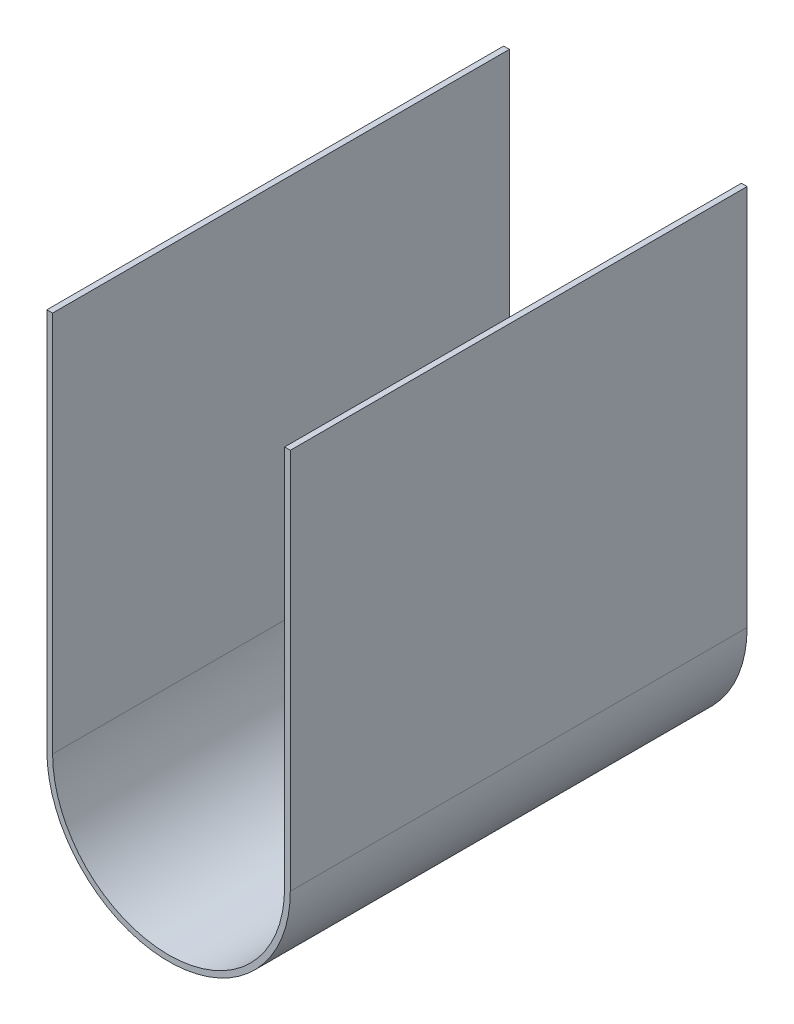
SolidWorks part; units mm, degrees
ref_plane "Front Plane" through (0, 0, 0) normal (0, 0, 1) x (1, 0, 0)
ref_plane "Top Plane" through (0, 0, 0) normal (0, 1, 0) x (1, 0, 0)
ref_plane "Right Plane" through (0, 0, 0) normal (1, 0, 0) x (0, 0, -1)
sketch "Sketch1" plane through (0, 0, 0) normal (0, 0, 1) x (1, 0, 0)
  line L1 (-32.5, -95) -> (32.5, -95)
  line L2 (-32.5, -95) -> (-32.5, 95)
  line L3 (-32.5, 95) -> (32.5, 95)
  line L4 (32.5, -95) -> (32.5, 95)
  line L5 (-32.5, -95) -> (32.5, 95) construction
  line L6 (-32.5, 95) -> (32.5, -95) construction
  line L7 (15.5, -110.5) -> (-15.5, -110.5)
  line L8 (15.5, -110.5) -> (15.5, -79.5)
  line L9 (15.5, -79.5) -> (-15.5, -79.5)
  line L10 (-15.5, -110.5) -> (-15.5, -79.5)
  line L11 (15.5, -110.5) -> (-15.5, -79.5) construction
  line L12 (15.5, -79.5) -> (-15.5, -110.5) construction
  circle A0 centre (0, -95) radius 32.5
  circle A1 centre (0, -95) radius 42 construction
  circle A2 centre (0, -95) radius 14
  point P0 (0, 0)
  point P14 (0, -127.5)
  dimension "D1" = 84
  dimension "D4" = 28
  dimension "D2" = 31
  dimension "D3" = 31
  dimension "D5" = 65
  dimension "D6" = 190
  dimension "D7" = 222.5
extrude "Boss-Extrude1" add sketch "Sketch1" along normal blind 6 contours A0 L4 L3 L2 | L1 A0 L10 L9 L8 | L1 A0 L8 L7 L10 | A2 L1 L10 L7 L8 | A2 L1 L8 L9 L10 region at (0, -78.7429, 0) region at (0, 12.6028, 0) region at (0, -111.2571, 0) region at (-15.1534, -87.25, 0) region at (-14.75, -95.3466, 0)
hole_wizard "M3 Clearance Hole1" positions "Sketch2" profile "Sketch3" hole size "M3" standard "ANSI Metric"
sketch "Sketch2" plane through (0, 0, 0) normal (0, 0, -1) x (-1, 0, 0)
  point P0 (-15.5, -110.5)
  point P3 (15.5, -110.5)
  point P6 (15.5, -79.5)
  point P9 (-15.5, -79.5)
sketch "Sketch3" plane through (15.5, -110.5, 0) normal (1, 0, 0) x (0, 1, 0)
  line L0 (0, 0) -> (0, 7.0815)
  line L1 (0, 7.0815) -> (1.8, 6)
  line L2 (1.8, 6) -> (1.8, 0)
  line L5 (1.8, 0) -> (0, 0)
  line L10 (0, 7.0815) -> (-1.8, 6) construction
  line L11 (0, -6.35) -> (0, 107.95) construction
  dimension "Hole Dia." = 3.6
  dimension "Hole Depth" = 6
  dimension "Drill Angle" = 118
fillet "Fillet1" radius 15 2 edges at (-32.5, 95, 3) (32.5, 95, 3)
sketch "Sketch4" plane through (0, 0, 6) normal (0, 0, 1) x (1, 0, 0)
  line L0 (32.5, -95) -> (32.5, 80) construction
  line L1 (32.5, -65) -> (-32.5, -65)
  line L2 (32.5, -65) -> (32.5, -56)
  line L3 (32.5, -56) -> (-32.5, -56)
  line L4 (-32.5, -65) -> (-32.5, -56)
  line L5 (-32.5, -95) -> (-32.5, 80) construction
  line L6 (0, 12) -> (0, 3)
  line L7 (32.5, 80) -> (-32.5, 80)
  line L8 (32.5, 80) -> (32.5, 71)
  line L9 (32.5, 71) -> (-32.5, 71)
  line L10 (-32.5, 80) -> (-32.5, 71)
  line L11 (-32.5, 12) -> (32.5, 12)
  line L12 (-32.5, 12) -> (-32.5, 3)
  line L13 (-32.5, 3) -> (32.5, 3)
  line L14 (32.5, 12) -> (32.5, 3)
  point P20 (0, 7.5)
  line M15 (-32.5, 80) -> (-32.5, -95)
  line M17 (32.5, -95) -> (32.5, 80)
  dimension "D1" = 9
  dimension "D2" = 9
  dimension "D3" = 9
  dimension "D4" = 30
  dimension "D5" = 127
  dimension "D6" = 63.5
extrude "Cut-Extrude1" cut sketch "Sketch4" against normal blind 2 contours L9 L7 M17 M15 | L13 L6 L11 M15 | L6 L13 L11 M17 | L3 L1 M17 M15 region at (0, -60.5, 6) region at (16.25, 7.5, 6) region at (-16.25, 7.5, 6) region at (0, 75.5, 6)
hole_wizard "M4 Clearance Hole1" positions "Sketch5" profile "Sketch6" hole size "M4" standard "ANSI Metric"
sketch "Sketch5" plane through (0, 0, 4) normal (0, 0, 1) x (1, 0, 0)
  line L0 (-32.5, 75.5) -> (32.5, 75.5)
  line L1 (-32.5, 80) -> (-32.5, 71) construction
  line L2 (32.5, 71) -> (32.5, 80) construction
  line L4 (-32.5, 7.5) -> (32.5, 7.5)
  line L5 (-32.5, 12) -> (-32.5, 3) construction
  line L6 (32.5, 3) -> (32.5, 12) construction
  line L8 (-32.5, -60.5) -> (32.5, -60.5)
  line L9 (-32.5, -56) -> (-32.5, -65) construction
  line L10 (32.5, -65) -> (32.5, -56) construction
  point P24 (-24.5, 75.5)
  point P26 (24.5, 75.5)
  point P28 (0, 75.5)
  point P30 (-24.5, 7.5)
  point P32 (0, 7.5)
  point P34 (24.5, 7.5)
  point P36 (24.5, -60.5)
  point P38 (0, -60.5)
  point P40 (-24.5, -60.5)
  dimension "D1" = 8
  dimension "D2" = 8
sketch "Sketch6" plane through (-24.5, -60.5, 4) normal (1, 0, 0) x (0, -1, 0)
  line L0 (0, 0) -> (0, 7.4421)
  line L1 (0, 7.4421) -> (2.4, 6)
  line L2 (2.4, 6) -> (2.4, 0)
  line L5 (2.4, 0) -> (0, 0)
  line L10 (0, 7.4421) -> (-2.4, 6) construction
  line L11 (0, -6.35) -> (0, 107.95) construction
  dimension "Hole Dia." = 4.8
  dimension "Hole Depth" = 6
  dimension "Drill Angle" = 118
chamfer "Chamfer1" distance 2.4 13 edges at (13.7, -110.5, 0) (-17.3, -110.5, 0) (-17.3, -79.5, 0) (13.7, -79.5, 0) (-22.1, 75.5, 0) (2.4, 75.5, 0) (26.9, 75.5, 0) (26.9, 7.5, 0) (2.4, 7.5, 0) (-22.1, 7.5, 0) (-22.1, -60.5, 0) (2.4, -60.5, 0) (26.9, -60.5, 0)
sketch "Sketch7" plane through (0, 0, 0) normal (0, 0, -1) x (-1, 0, 0)
  line L0 (34.1, -95) -> (34.1, 80)
  line L1 (17.5, 96.6) -> (-17.5, 96.6)
  line L2 (-34.1, 80) -> (-34.1, -95)
  line L3 (32.5, -95) -> (32.5, 80)
  line L4 (17.5, 95) -> (-17.5, 95)
  line L5 (-32.5, 80) -> (-32.5, -95)
  line L6 (32.5, -95) -> (32.5, 80)
  line L7 (17.5, 95) -> (-17.5, 95)
  line L8 (-32.5, 80) -> (-32.5, -95)
  line L9 (-32.5, 80) -> (-34.1, 80)
  line L10 (32.5, 80) -> (34.1, 80)
  arc A0 (34.1, 80) -> (17.5, 96.6) centre (17.5, 80) ccw
  arc A1 (-17.5, 96.6) -> (-34.1, 80) centre (-17.5, 80) ccw
  arc A2 (-34.1, -95) -> (34.1, -95) centre (0, -95) ccw
  arc A3 (32.5, 80) -> (17.5, 95) centre (17.5, 80) ccw
  arc A4 (-17.5, 95) -> (-32.5, 80) centre (-17.5, 80) ccw
  arc A5 (-32.5, -95) -> (32.5, -95) centre (0, -95) ccw
  arc A6 (32.5, 80) -> (17.5, 95) centre (17.5, 80) ccw
  arc A7 (-17.5, 95) -> (-32.5, 80) centre (-17.5, 80) ccw
  arc A8 (-32.5, -95) -> (32.5, -95) centre (0, -95) ccw
  line M30 (-32.5, 80) -> (-32.5, -95)
  arc M31 (-32.5, -95) -> (32.5, -95) centre (0, -95) ccw
  dimension "D1" = 0
  dimension "D2" = 1.6
extrude "Boss-Extrude2" add sketch "Sketch7" against normal blind 128 separate body contours L2 A2 L9 M31 M30 region at (0, -128.8801, 0)
delete or keep bodies "Body-Delete/Keep 2" type delete bodies bodies 104
sketch "Sketch10" plane through (34.1, 0, 0) normal (1, 0, 0) x (0, 0, -1)
  line L0 (0, 80) -> (0, -95) construction
  line L1 (-128, 80) -> (0, 80)
  line L2 (-128, 80) -> (-128, 12)
  line L3 (-128, 12) -> (0, 12)
  line L4 (0, 80) -> (0, 12)
  line L5 (-128, -95) -> (0, -95) construction
  dimension "D1" = 107
extrude "Cut-Extrude2" cut sketch "Sketch10" against normal through all
